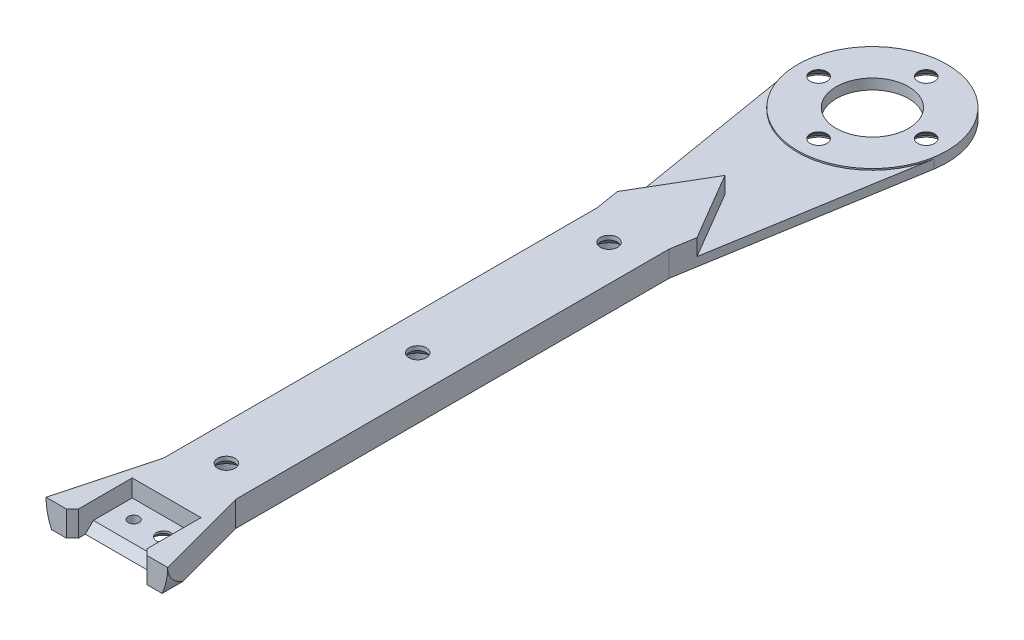
SolidWorks part; units mm, degrees
ref_plane "Front Plane" through (0, 0, 0) normal (0, 0, 1) x (1, 0, 0)
ref_plane "Top Plane" through (0, 0, 0) normal (0, 1, 0) x (1, 0, 0)
ref_plane "Right Plane" through (0, 0, 0) normal (1, 0, 0) x (0, 0, -1)
sketch "Sketch1" plane through (0, 0, 0) normal (0, 1, 0) x (1, 0, 0)
  line L0 (-12.3296, -2.0568) -> (-6, -40)
  line L1 (-6, -40) -> (6, -40)
  line L2 (6, -40) -> (12.3296, -2.0568)
  arc A0 (12.3296, -2.0568) -> (-12.3296, -2.0568) centre (0, 0) ccw
  dimension "D1" = 25
  dimension "D2" = 40
  dimension "D3" = 12
extrude "Boss-Extrude1" add sketch "Sketch1" along normal blind 1.5
sketch "Sketch2" plane through (0, 1.5, 0) normal (0, 1, 0) x (1, 0, 0)
  line L0 (6, -40) -> (12.3296, -2.0568) construction
  line L1 (-6, -40) -> (6, -40) construction
  line L2 (-12.3296, -2.0568) -> (-6, -40) construction
  line L3 (6, -40) -> (12.3296, -2.0568) construction
  line L4 (-6, -40) -> (6, -40) construction
  line L5 (-12.3296, -2.0568) -> (-6, -40) construction
  line L6 (-6, -40) -> (-1.5641, -13.4091)
  line L7 (6, -40) -> (1.5641, -13.4091)
  line L8 (-6, -40) -> (6, -40)
  line L9 (1.5641, -13.4091) -> (-1.5641, -13.4091) construction
  line L10 (1.5641, -13.4091) -> (10.4359, -13.4091) construction
  circle A0 centre (0, 0) radius 13.5 construction
  arc A1 (-1.5641, -13.4091) -> (1.5641, -13.4091) centre (0, 0) ccw
  point P10 (0, -13.4091)
  point P12 (6, -13.4091)
  dimension "D1" = 27
extrude "Boss-Extrude2" [suppressed] add sketch "Sketch2" along normal blind 2.15
sketch "Sketch3" plane through (0, 0, 0) normal (0, -1, 0) x (1, 0, 0)
  circle A0 centre (0, 0) radius 9 construction
  circle A1 centre (0, 9) radius 1.25
  circle A2 centre (9, 0) radius 1.25
  circle A3 centre (0, -9) radius 1.25
  circle A4 centre (-9, 0) radius 1.25
  point P14 (0, 0)
  dimension "D1" = 18
  dimension "D2" = 2.5
  dimension "D3" = 4
hole_wizard "CSK for M2.5 Flat Head Machine Screw1" positions "Sketch4" profile "Sketch5" countersink size "M2.5" standard "ANSI Metric" end condition through all
sketch "Sketch4" plane through (0, 0, 0) normal (0, -1, 0) x (-1, 0, 0)
  point P0 (0, -9)
  point P3 (9, 0)
  point P6 (0, 9)
  point P9 (-9, 0)
sketch "Sketch5" plane through (0, 0, 9) normal (1, 0, 0) x (0, 0, -1)
  line L0 (0, 0) -> (0, 1.5)
  line L1 (0, 1.5) -> (1.4, 1.5)
  line L2 (1.4, 1.5) -> (1.4, 1.35)
  line L3 (1.4, 1.35) -> (2.75, 0)
  line L5 (2.75, 0) -> (0, 0)
  line L6 (-1.4, 1.35) -> (-2.75, 0) construction
  line L11 (0, -6.35) -> (0, 107.95) construction
  dimension "Thru Hole Dia." = 2.8
  dimension "Thru Hole Depth" = 1.5
  dimension "Near C'Sink Dia." = 5.5
  dimension "Near C'Sink Angle" = 90
sketch "Sketch6" plane through (0, 0, 0) normal (0, -1, 0) x (1, 0, 0)
  circle A0 centre (0, 0) radius 6.05
  dimension "D1" = 12.1
extrude "Cut-Extrude1" cut sketch "Sketch6" against normal through all
sketch "Sketch7" plane through (0, 0, 0) normal (0, -1, 0) x (-1, 0, 0)
  line L0 (0, 0) -> (0, -40) construction
  line L1 (6, -40) -> (-6, -40) construction
  circle A0 centre (0, -35) radius 2.75
  circle A1 centre (0, 0) radius 6.05 construction
  dimension "D2" = 5.5
  dimension "D1" = 5
extrude "Cut-Extrude2" [suppressed] cut sketch "Sketch7" against normal blind 1
hole_wizard "CSK for M2.5 Flat Head Machine Screw2" [suppressed] positions "Sketch8" profile "Sketch9" countersink size "M2.5" standard "ANSI Metric"
sketch "Sketch8" [suppressed] plane through (0, 1, 0) normal (0, -1, 0) x (-1, 0, 0)
  point P0 (0, -20)
sketch "Sketch9" plane through (0, 1, 20) normal (1, 0, 0) x (0, 0, -1)
  line L0 (0, 0) -> (0, 8.8712)
  line L1 (0, 8.8712) -> (1.45, 8)
  line L2 (1.45, 8) -> (1.45, 1.3)
  line L3 (1.45, 1.3) -> (2.75, 0)
  line L5 (2.75, 0) -> (0, 0)
  line L6 (-1.45, 1.3) -> (-2.75, 0) construction
  line L10 (0, 8.8712) -> (-1.45, 8) construction
  line L11 (0, -6.35) -> (0, 107.95) construction
  dimension "Hole Dia." = 2.9
  dimension "Hole Depth" = 8
  dimension "Near C'Sink Dia." = 5.5
  dimension "Near C'Sink Angle" = 90
  dimension "Drill Angle" = 118
sketch "Sketch10" plane through (0, 0, 0) normal (0, -1, 0) x (1, 0, 0)
  line L3 (12.3296, 2.0568) -> (6, 40)
  line L4 (6, 40) -> (-6, 40)
  line L5 (-6, 40) -> (-12.3296, 2.0568)
  line L6 (12.3296, 2.0568) -> (6, 40)
  line L7 (6, 40) -> (-6, 40)
  line L8 (-6, 40) -> (-12.3296, 2.0568)
  circle A0 centre (0, 0) radius 6.05 construction
  arc A1 (-12.3296, 2.0568) -> (12.3296, 2.0568) centre (0, 0) ccw
  arc A2 (-12.3296, 2.0568) -> (12.3296, 2.0568) centre (0, 0) ccw
  circle A3 centre (9, 0) radius 2.75 construction
  circle A4 centre (0, -9) radius 2.75 construction
  circle A5 centre (-9, 0) radius 2.75 construction
  circle A6 centre (0, 9) radius 2.75 construction
  circle A7 centre (0, 0) radius 6.05
  circle A8 centre (9, 0) radius 2.75
  circle A9 centre (0, -9) radius 2.75
  circle A10 centre (-9, 0) radius 2.75
  circle A11 centre (0, 9) radius 2.75
  dimension "D1" = 0
extrude "Boss-Extrude3" add sketch "Sketch10" along normal blind 0.2368
sketch "Sketch11" plane through (0, 1.5, 0) normal (0, 1, 0) x (1, 0, 0)
  line L0 (0, 0) -> (0, -40) construction
  line L1 (-6, -40) -> (6, -40) construction
  line L2 (-6, -40) -> (-6.6673, -36) construction
  line L3 (-12.3296, -2.0568) -> (-6, -40) construction
  line L4 (-6.6673, -36) -> (10.7753, -6.3359) construction
  line L5 (-6, -40) -> (-6.6673, -36)
  line L6 (-6.6673, -36) -> (0, -24.6611)
  line L7 (6.6673, -36) -> (0, -24.6611)
  line L8 (6, -40) -> (6.6673, -36)
  line L9 (-6, -40) -> (6, -40)
  circle A0 centre (0, 0) radius 12.5 construction
  dimension "D1" = 4
sketch "Sketch12" plane through (0, 1.5, 0) normal (0, 1, 0) x (1, 0, 0)
  line L3 (-12.3296, -2.0568) -> (-6, -40)
  line L4 (-6, -40) -> (6, -40)
  line L5 (6, -40) -> (12.3296, -2.0568)
  line L6 (-12.3296, -2.0568) -> (-6, -40)
  line L7 (-6, -40) -> (6, -40)
  line L8 (6, -40) -> (12.3296, -2.0568)
  arc A0 (-12.3296, -2.0568) -> (12.3296, -2.0568) centre (0, 0) ccw
  circle A1 centre (0, 0) radius 12.5 construction
  arc A3 (12.3296, -2.0568) -> (-12.3296, -2.0568) centre (0, 0) ccw
  dimension "D1" = 0
extrude "Cut-Extrude3" cut sketch "Sketch12" against normal blind 0.25
extrude "Boss-Extrude4" add sketch "Sketch11" along normal blind 2.5 and the other way up to next
sketch "Sketch13" plane through (0, 0, 40) normal (0, 0, 1) x (1, 0, 0)
  line L0 (0, 1.5) -> (0, 3.65) construction
  line L1 (12.5, 1.5) -> (-12.5, 1.5) construction
  circle A0 centre (0, 3.65) radius 3
  dimension "D2" = 6
  dimension "D1" = 2.15
extrude "Cut-Extrude4" [suppressed] cut sketch "Sketch13" against normal up to vertex
sketch "Sketch14" [suppressed] plane through (0, 3.5, 0) normal (0, 1, 0) x (1, 0, 0)
  line L0 (-4.0962, -35.4) -> (-2.9962, -35.4) construction
  line L1 (-2.9962, -35.4) -> (-2.9962, -37.6) construction
  line L2 (-2.9962, -37.6) -> (-4.0962, -37.6) construction
  line L3 (-4.0962, -35.4) -> (-2.9962, -35.4)
  line L4 (-2.9962, -35.4) -> (-2.9962, -37.6)
  line L5 (-2.9962, -37.6) -> (-4.0962, -37.6)
  arc A0 (-4.0962, -35.4) -> (-4.0962, -37.6) centre (-4.0962, -36.5) ccw construction
  arc A1 (-4.0962, -35.4) -> (-4.0962, -37.6) centre (-4.0962, -36.5) ccw
extrude "Cut-Extrude5" [suppressed] cut sketch "Sketch14" against normal through all contours L5 A1 L3 L4
sketch "Sketch15" [suppressed] plane through (0, -0.75, 0) normal (0, -1, 0) x (1, 0, 0)
  line L1 (-4.0962, 37.6) -> (-2.8962, 37.6)
  line L2 (-2.8962, 37.6) -> (-2.8962, 35.4)
  line L3 (-2.8962, 35.4) -> (-4.0962, 35.4)
  line L4 (-2.9962, 35.4) -> (-2.9962, 37.6) construction
  circle A0 centre (-4.0962, 36.5) radius 1.1 construction
  arc A1 (-4.0962, 37.6) -> (-4.0962, 35.4) centre (-4.0962, 36.5) cw
  dimension "D1" = 0.1
extrude "Boss-Extrude5" [suppressed] add sketch "Sketch15" against normal offset from surface (3.25 mm away) 1
sketch "Sketch16" [suppressed] plane through (0, 0, 37.6) normal (0, 0, -1) x (-1, 0, 0)
  line L0 (2.9962, 2.5) -> (2.9962, 3.5)
  line L1 (2.9962, 3.5) -> (2.7406, 2.4297)
  line L2 (2.9962, 2.5) -> (4.0962, 2.5) construction
  arc A0 (2.9962, 2.5) -> (2.7406, 2.4297) centre (2.9962, 2) ccw
  arc A1 (0, 0.65) -> (2.9962, 3.5) centre (0, 3.65) ccw construction
  dimension "D1" = 0.5
extrude "Cut-Extrude6" [suppressed] cut sketch "Sketch16" along normal up to surface (2.2 mm away)
hole_wizard "CSK for M2 Flat Head Machine Screw1" [suppressed] positions "Sketch18" profile "Sketch19" countersink size "M2" standard "ANSI Metric"
sketch "Sketch18" [suppressed] plane through (0, -0.75, 0) normal (0, -1, 0) x (-1, 0, 0)
  point P0 (4.0962, -36.5)
sketch "Sketch19" plane through (-4.0962, -0.75, 36.5) normal (1, 0, 0) x (0, 0, -1)
  line L0 (0, 0) -> (0, 4.25)
  line L1 (0, 4.25) -> (1.1, 4.25)
  line L2 (1.1, 4.25) -> (1.1, 1.1)
  line L3 (1.1, 1.1) -> (2.2, 0)
  line L5 (2.2, 0) -> (0, 0)
  line L6 (-1.1, 1.1) -> (-2.2, 0) construction
  line L11 (0, -6.35) -> (0, 107.95) construction
  dimension "Thru Hole Dia." = 2.2
  dimension "Thru Hole Depth" = 4.25
  dimension "Near C'Sink Dia." = 4.4
  dimension "Near C'Sink Angle" = 90
mirror "Mirror1" [suppressed] about plane through (0, 0, 0) normal (1, 0, 0)
sketch "Sketch20" plane through (0, -0.2368, 0) normal (0, -1, 0) x (1, 0, 0)
  line L0 (6, 40) -> (-6, 40) construction
  line L1 (-6, 40) -> (6, 40) construction
  line L2 (-6, 40) -> (-6, 148.05) construction
  line L3 (-6, 148.05) -> (6, 148.05) construction
  line L4 (6, 40) -> (6, 148.05) construction
  line L5 (0, 148.05) -> (0, 0) construction
  line L6 (14.4889, 144.1677) -> (6, 112.4868) construction
  line L7 (-14.4889, 144.1677) -> (-6, 112.4868) construction
  line L8 (-10.1702, 128.05) -> (10.1702, 128.05) construction
  line L9 (-6, 40) -> (-6, 112.4868)
  line L10 (-6, 112.4868) -> (-10.1702, 128.05)
  line L11 (-10.1702, 128.05) -> (10.1702, 128.05)
  line L12 (10.1702, 128.05) -> (6, 112.4868)
  line L13 (6, 112.4868) -> (6, 40)
  line L14 (6, 40) -> (-6, 40)
  circle A0 centre (0, 148.05) radius 15 construction
  dimension "D1" = 30
  dimension "D2" = 148.05
  dimension "D3" = 15
  dimension "D4" = 20
extrude "Boss-Extrude6" add sketch "Sketch20" against normal up to surface (4.2368 mm away) up to face at (0, 4, 35.3322)
sketch "Sketch21" plane through (0, 0, 128.05) normal (0, 0, 1) x (1, 0, 0)
  line L0 (10.1702, 4) -> (-10.1702, 4) construction
  circle A0 centre (0, 4) radius 10.1702
  circle A1 centre (0, 4) radius 12.7475
extrude "Cut-Extrude7" cut sketch "Sketch21" against normal blind 10
sketch "Sketch22" plane through (0, 0, 128.05) normal (0, 0, 1) x (1, 0, 0)
  line L0 (10.1702, 4) -> (-10.1702, 4) construction
  line L1 (-5.75, 6.9) -> (5.75, 6.9)
  line L2 (-5.75, 6.9) -> (-5.75, 1.1)
  line L3 (-5.75, 1.1) -> (5.75, 1.1)
  line L4 (5.75, 6.9) -> (5.75, 1.1)
  line L5 (-5.75, 6.9) -> (5.75, 1.1) construction
  line L6 (-5.75, 1.1) -> (5.75, 6.9) construction
  line L8 (9.2456, -0.2368) -> (-9.2456, -0.2368) construction
  point P0 (0, 4)
  dimension "D1" = 5.8
  dimension "D2" = 11.5
  dimension "D3" = 1.3368
extrude "Cut-Extrude8" cut sketch "Sketch22" against normal blind 10
sketch "Sketch23" plane through (0, 0, 0) normal (1, 0, 0) x (0, 0, -1)
  line L0 (-124.55, 1.1) -> (-128.05, -2.4)
  line L2 (-128.05, -2.4) -> (-128.05, 1.1)
  line L3 (-128.05, 1.1) -> (-124.55, 1.1)
  line L4 (-128.05, 4) -> (-128.05, 1.1) construction
  dimension "D1" = 3.5
extrude "Cut-Extrude9" cut sketch "Sketch23" against normal up to surface and the other way up to surface up to face at (-5.75, 2.55, 123.05) other way up to face at (5.75, 2.55, 123.05)
chamfer "Chamfer1" distance 1 angle 45 2 edges at (5.75, 1.8816, 128.05) (-5.75, 1.8816, 128.05)
sketch "Sketch24" plane through (0, 4, 0) normal (0, 1, 0) x (1, 0, 0)
  line L0 (0, 0) -> (0, -118.05) construction
  line L1 (-5.75, -118.05) -> (5.75, -118.05) construction
  line L2 (-6.75, -128.05) -> (-10.1702, -128.05) construction
  circle A0 centre (0, -108.05) radius 1.25
  circle A1 centre (0, -76.05) radius 1.25
  circle A2 centre (0, -44.05) radius 1.25
  circle A3 centre (2.5, -121.05) radius 1.25
  point P15 (0, 0)
  point P16 (2.5109, -121.05)
  dimension "D1" = 2.5
  dimension "D2" = 20
  dimension "D4" = 32
  dimension "D5" = 7
  dimension "D6" = 2.5
  dimension "D3" = 3
sketch "Sketch27" plane through (0, 4, 0) normal (0, 1, 0) x (1, 0, 0)
  line L0 (-6, -112.4868) -> (-6, -40) construction
  line L1 (6, -40) -> (6, -112.4868) construction
  line L2 (6, -40) -> (6.6673, -36) construction
  line L3 (-6.6673, -36) -> (-6, -40) construction
  line L4 (6.6673, -36) -> (0, -24.6611) construction
  line L5 (0, -24.6611) -> (-6.6673, -36) construction
  line L6 (-6, -112.4868) -> (-6, -40) construction
  line L7 (6, -40) -> (6, -112.4868) construction
  line L8 (6, -40) -> (6.6673, -36) construction
  line L9 (-6.6673, -36) -> (-6, -40) construction
  line L10 (6.6673, -36) -> (0, -24.6611) construction
  line L11 (0, -24.6611) -> (-6.6673, -36) construction
  line L12 (-4.5, -112.4868) -> (-4.5, -39.8757)
  line L13 (-5.0981, -36.2906) -> (-4.5, -39.8757)
  line L14 (0, -27.6205) -> (-5.0981, -36.2906)
  line L15 (5.0981, -36.2906) -> (0, -27.6205)
  line L16 (4.5, -39.8757) -> (5.0981, -36.2906)
  line L17 (4.5, -39.8757) -> (4.5, -112.4868)
  line L18 (-4.5, -112.4868) -> (4.5, -112.4868)
  dimension "D1" = 1.5
extrude "Cut-Extrude11" [suppressed] cut sketch "Sketch27" against normal offset from surface (2.4 mm away) 2
sketch "Sketch28" [suppressed] plane through (0, 1.25, 0) normal (0, 1, 0) x (1, 0, 0)
  circle A0 centre (0, -33.05) radius 2
  circle A1 centre (0, -63.05) radius 2
  circle A2 centre (0, -93.05) radius 2
  dimension "D1" = 4
extrude "Boss-Extrude7" [suppressed] add sketch "Sketch28" along normal up to surface (2.4 mm away)
sketch "Sketch25" plane through (0, -0.2368, 0) normal (0, -1, 0) x (1, 0, 0)
  circle A0 centre (0, 108.05) radius 2.75
  circle A1 centre (0, 76.05) radius 2.75
  circle A2 centre (0, 44.05) radius 2.75
  dimension "D1" = 5.5
extrude "Cut-Extrude10" cut sketch "Sketch25" against normal offset from surface (2.2368 mm away) 2 up to face at (0, 4, 93.6023)
hole_wizard "CSK for M2.5 Flat Head Machine Screw3" positions "Sketch31" profile "Sketch30" countersink size "M2.5" standard "ANSI Metric" end condition through all
sketch "Sketch31" plane through (0, 2, 0) normal (0, -1, 0) x (-1, 0, 0)
  point P0 (0, -44.05)
  point P3 (0, -76.05)
  point P6 (0, -108.05)
sketch "Sketch30" plane through (0, 2, 44.05) normal (1, 0, 0) x (0, 0, -1)
  line L0 (0, 0) -> (0, 2)
  line L1 (0, 2) -> (1.45, 2)
  line L2 (1.45, 2) -> (1.45, 1.3)
  line L3 (1.45, 1.3) -> (2.75, 0)
  line L5 (2.75, 0) -> (0, 0)
  line L6 (-1.45, 1.3) -> (-2.75, 0) construction
  line L11 (0, -6.35) -> (0, 107.95) construction
  dimension "Thru Hole Dia." = 2.9
  dimension "Thru Hole Depth" = 2
  dimension "Near C'Sink Dia." = 5.5
  dimension "Near C'Sink Angle" = 90
hole_wizard "CSK for M2 Flat Head Machine Screw2" positions "Sketch32" profile "Sketch33" countersink size "M2" standard "ANSI Metric" end condition through all
sketch "Sketch32" plane through (0, -0.2368, 0) normal (0, -1, 0) x (-1, 0, 0)
  point P0 (-2.5, -121.05)
sketch "Sketch33" plane through (2.5, -0.2368, 121.05) normal (1, 0, 0) x (0, 0, -1)
  line L0 (0, 0) -> (0, 4.2368)
  line L1 (0, 4.2368) -> (1.2, 4.2368)
  line L2 (1.2, 4.2368) -> (1.2, 1)
  line L3 (1.2, 1) -> (2.2, 0)
  line L5 (2.2, 0) -> (0, 0)
  line L6 (-1.2, 1) -> (-2.2, 0) construction
  line L11 (0, -6.35) -> (0, 107.95) construction
  dimension "Thru Hole Dia." = 2.4
  dimension "Thru Hole Depth" = 4.2368
  dimension "Near C'Sink Dia." = 4.4
  dimension "Near C'Sink Angle" = 90
sketch "Sketch34" plane through (0, -0.2368, 0) normal (0, -1, 0) x (1, 0, 0)
  circle A3 centre (-2.5, 121.05) radius 1 construction
  circle A4 centre (-2.5, 121.05) radius 1 construction
  circle A5 centre (-2.5, 121.05) radius 0.9
  dimension "D1" = 1.8
extrude "Cut-Extrude12" cut sketch "Sketch34" against normal blind 10 contours A5
